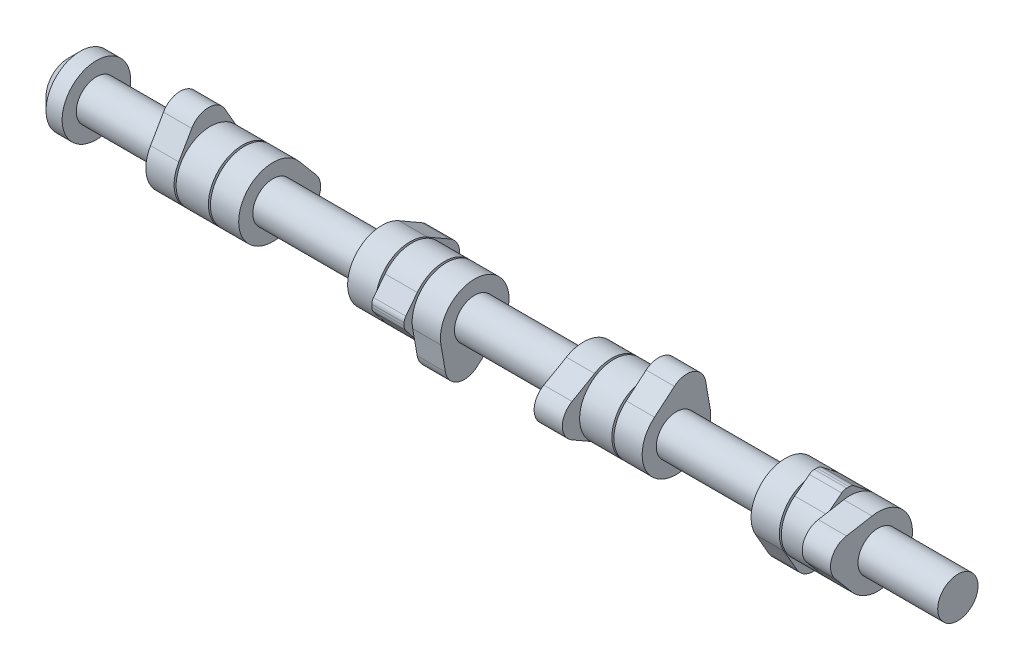
SolidWorks part; units mm, degrees
note: The reader was unsure of these and kept them because the rebuilt part matched: shared geometry of "Sketch1<5>", "Sketch1<6>".
ref_plane "Front Plane" through (0, 0, 0) normal (0, 0, 1) x (1, 0, 0)
ref_plane "Top Plane" through (0, 0, 0) normal (0, 1, 0) x (1, 0, 0)
ref_plane "Right Plane" through (0, 0, 0) normal (1, 0, 0) x (0, 0, -1)
sketch "Sketch1" plane through (0, 0, 0) normal (0, 0, 1) x (1, 0, 0)
  line L0 (0, 0) -> (10, 0)
  line L1 (10, 0) -> (46.5, 0)
  line L2 (46.5, 0) -> (78.5, 0)
  line L3 (78.5, 0) -> (146.5, 0)
  line L4 (146.5, 0) -> (178.5, 0)
  line L5 (178.5, 0) -> (246.5, 0)
  line L6 (246.5, 0) -> (278.5, 0)
  line L7 (278.5, 0) -> (346.5, 0)
  line L8 (346.5, 0) -> (378.5, 0)
  line L9 (378.5, 0) -> (415, 0)
  line L10 (415, 0) -> (425, 0)
  line L11 (39.5, 0) -> (53.5, 0) construction
  line L12 (71.5, 0) -> (85.5, 0) construction
  line L13 (139.5, 0) -> (153.5, 0) construction
  line L14 (185.5, 0) -> (171.5, 0) construction
  line L15 (239.5, 0) -> (253.5, 0)
  line L16 (271.5, 0) -> (285.5, 0)
  line L17 (339.5, 0) -> (353.5, 0)
  line L18 (371.5, 0) -> (385.5, 0)
  line L19 (139.5, 0) -> (139.5, 7)
  line L20 (0, 0) -> (425, 0)
  line L21 (0, 0) -> (0, -10)
  line L22 (0, -10) -> (425, -10)
  line L23 (425, 0) -> (425, -10)
  line L24 (39.5, 0) -> (53.5, 0)
  line L25 (39.5, 0) -> (39.5, 7)
  line L26 (39.5, 7) -> (53.5, 7)
  line L27 (53.5, 0) -> (53.5, 7)
  line L28 (85.5, 0) -> (71.5, 0)
  line L29 (85.5, 0) -> (85.5, 7)
  line L30 (85.5, 7) -> (71.5, 7)
  line L31 (71.5, 0) -> (71.5, 7)
  line L32 (139.5, 0) -> (153.5, 0)
  line L33 (153.5, 0) -> (153.5, 7)
  line L34 (139.5, 7) -> (153.5, 7)
  line L35 (185.5, 0) -> (185.5, 7)
  line L36 (185.5, 0) -> (171.5, 0)
  line L37 (171.5, 0) -> (171.5, 7)
  line L38 (185.5, 7) -> (171.5, 7)
  line L39 (239.5, 0) -> (239.5, 7)
  line L40 (239.5, 0) -> (253.5, 0)
  line L41 (253.5, 0) -> (253.5, 7)
  line L42 (239.5, 7) -> (253.5, 7)
  line L43 (285.5, 0) -> (285.5, 7)
  line L44 (285.5, 0) -> (271.5, 0)
  line L45 (271.5, 0) -> (271.5, 7)
  line L46 (285.5, 7) -> (271.5, 7)
  line L47 (339.5, 0) -> (339.5, 7)
  line L48 (339.5, 0) -> (353.5, 0)
  line L49 (353.5, 0) -> (353.5, 7)
  line L50 (339.5, 7) -> (353.5, 7)
  line L51 (385.5, 0) -> (385.5, 7)
  line L52 (385.5, 0) -> (371.5, 0)
  line L53 (371.5, 0) -> (371.5, 7)
  line L54 (385.5, 7) -> (371.5, 7)
  line L55 (53.5, 0) -> (54.5, 0)
  line L56 (54.5, 0) -> (70.5, 0)
  line L57 (70.5, 0) -> (71.5, 0)
  line L58 (154.5, 0) -> (154.5, 7)
  line L59 (54.5, 0) -> (70.5, 0)
  line L60 (54.5, 0) -> (54.5, 7)
  line L61 (54.5, 7) -> (70.5, 7)
  line L62 (70.5, 0) -> (70.5, 7)
  line L63 (154.5, 0) -> (170.5, 0)
  line L64 (170.5, 0) -> (170.5, 7)
  line L65 (154.5, 7) -> (170.5, 7)
  line L66 (254.5, 0) -> (254.5, 7)
  line L67 (254.5, 0) -> (270.5, 0)
  line L68 (270.5, 0) -> (270.5, 7)
  line L69 (254.5, 7) -> (270.5, 7)
  line L70 (354.5, 0) -> (354.5, 7)
  line L71 (354.5, 0) -> (370.5, 0)
  line L72 (370.5, 0) -> (370.5, 7)
  line L73 (354.5, 7) -> (370.5, 7)
  point P16 (46.5, 0)
  point P19 (78.5, 0)
  point P22 (146.5, 0)
  point P25 (178.5, 0)
  point P28 (246.5, 0)
  point P31 (278.5, 0)
  point P34 (346.5, 0)
  point P37 (378.5, 0)
  dimension "D1" = 10
  dimension "D2" = 36.5
  dimension "D3" = 32
  dimension "D4" = 68
  dimension "D5" = 32
  dimension "D6" = 68
  dimension "D7" = 32
  dimension "D8" = 68
  dimension "D9" = 32
  dimension "D10" = 36.5
  dimension "D11" = 10
  dimension "D12" = 14
  dimension "D13" = 14
  dimension "D14" = 14
  dimension "D15" = 14
  dimension "D16" = 14
  dimension "D17" = 14
  dimension "D18" = 14
  dimension "D19" = 14
  dimension "D20" = 10
  dimension "D21" = 7
  dimension "D23" = 1
  dimension "D24" = 1
  dimension "D25" = 16
  dimension "D22" = 4
  dimension "D26" = 4
revolve "Revolve1" add sketch "Sketch1" angle 360 about L22
revolve "Revolve2" add sketch "Sketch1<5>" angle 360 about L22
sketch "Sketch1<5>" plane through (0, 0, 0) normal (0, 0, 1) x (1, 0, 0) same geometry as "Sketch1"
sketch "Sketch2" plane through (39.5, 0, 0) normal (-1, 0, 0) x (0, 0, 1)
  line L0 (0, 0) -> (0, 7)
  line L1 (0, 7) -> (0, 15)
  line L2 (-6, 15) -> (6, 15)
  line L3 (-6, 15) -> (-17, -10)
  line L4 (-17, -10) -> (0, -10)
  line L5 (0, -10) -> (17, -10)
  line L6 (17, -10) -> (6, 15)
  circle A0 centre (0, -10) radius 17 construction
  point P11 (0, 15)
  circle M4 centre (0, -10) radius 17
  dimension "D1" = 8
  dimension "D2" = 7
  dimension "D3" = 12
extrude "Boss-Extrude2" add sketch "Sketch2" against normal blind 14 contours L6 L2 L1 M4 | L2 L3 L1 M4
fillet "Fillet3" radius 9.5 4 edges at (39.5, 15, 0) (46.5, 15, -6) (46.5, 15, 6) (53.5, 15, 0)
fillet "Fillet5" radius 1000 2 edges at (46.5, 2.5335, 11.4853) (46.5, 2.5335, -11.4853)
sketch "Lobe sketch" plane through (39.5, 0, 0) normal (-1, 0, 0) x (0, 0, 1)
  arc A15 (-14.6833, -1.4325) -> (14.6833, -1.4325) centre (0, -10) ccw
  arc A16 (8.2663, 9.7295) -> (14.6833, -1.4325) centre (878.4044, 502.5375) ccw
  arc A17 (8.2663, 9.7295) -> (-8.2663, 9.7295) centre (0, 5.0479) ccw
  arc A18 (-14.6833, -1.4325) -> (-8.2663, 9.7295) centre (-878.4044, 502.5375) ccw
  arc A19 (-14.6833, -1.4325) -> (14.6833, -1.4325) centre (0, -10) ccw
  arc A20 (8.2663, 9.7295) -> (14.6833, -1.4325) centre (878.4044, 502.5375) ccw
  arc A21 (8.2663, 9.7295) -> (-8.2663, 9.7295) centre (0, 5.0479) ccw
  arc A22 (-14.6833, -1.4325) -> (-8.2663, 9.7295) centre (-878.4044, 502.5375) ccw
  dimension "D1" = 0
sketch "Sketch10" plane through (71.5, 0, 0) normal (-1, 0, 0) x (0, 0, 1)
  circle A1 centre (0, -10) radius 17
  circle A2 centre (0, -10) radius 17
  arc A6 (-14.6833, -1.4325) -> (14.6833, -1.4325) centre (0, -10) ccw
  arc A7 (8.2663, 9.7295) -> (14.6833, -1.4325) centre (878.4044, 502.5375) ccw
  arc A8 (8.2663, 9.7295) -> (-8.2663, 9.7295) centre (0, 5.0479) ccw
  arc A9 (-14.6833, -1.4325) -> (-8.2663, 9.7295) centre (-878.4044, 502.5375) ccw
  arc A10 (-14.6833, -1.4325) -> (14.6833, -1.4325) centre (0, -10) ccw
  arc A11 (8.2663, 9.7295) -> (14.6833, -1.4325) centre (878.4044, 502.5375) ccw
  arc A12 (8.2663, 9.7295) -> (-8.2663, 9.7295) centre (0, 5.0479) ccw
  arc A13 (-14.6833, -1.4325) -> (-8.2663, 9.7295) centre (-878.4044, 502.5375) ccw
  circle M6 centre (0, -10) radius 17
  dimension "D1" = 0
  dimension "D2" = 0
extrude "Boss-Extrude5" add sketch "Sketch10" against normal blind 14 contours A13 A11 A12 M6
sketch "Sketch11" plane through (239.5, 0, 0) normal (-1, 0, 0) x (0, 0, 1)
  circle A3 centre (0, -10) radius 17
  arc A11 (19.7295, -18.2663) -> (19.7295, -1.7337) centre (15.0479, -10) ccw
  arc A12 (19.7295, -18.2663) -> (8.5675, -24.6833) centre (512.5375, -888.4044) ccw
  arc A13 (8.5675, 4.6833) -> (8.5675, -24.6833) centre (0, -10) ccw
  arc A14 (8.5675, 4.6833) -> (19.7295, -1.7337) centre (512.5375, 868.4044) ccw
  circle M6 centre (0, -10) radius 17
extrude "Boss-Extrude6" add sketch "Sketch11" against normal blind 14 contours A14 A12 A11 M6
sketch "Sketch12" plane through (271.5, 0, 0) normal (-1, 0, 0) x (0, 0, 1)
  circle A1 centre (0, -10) radius 17
  circle A2 centre (0, -10) radius 17
  arc A10 (19.7295, -18.2663) -> (19.7295, -1.7337) centre (15.0479, -10) ccw
  arc A11 (19.7295, -18.2663) -> (8.5675, -24.6833) centre (512.5375, -888.4044) ccw
  arc A12 (8.5675, 4.6833) -> (8.5675, -24.6833) centre (0, -10) ccw
  arc A13 (8.5675, 4.6833) -> (19.7295, -1.7337) centre (512.5375, 868.4044) ccw
  dimension "D1" = 0
extrude "Boss-Extrude7" add sketch "Sketch12" against normal blind 14 contours A10 A13 A12 A11
sketch "Sketch13" plane through (339.5, 0, 0) normal (-1, 0, 0) x (0, 0, 1)
  circle A1 centre (0, -10) radius 17
  circle A2 centre (0, -10) radius 17
  arc A10 (-8.2663, -29.7295) -> (8.2663, -29.7295) centre (0, -25.0479) ccw
  arc A11 (-8.2663, -29.7295) -> (-14.6833, -18.5675) centre (-878.4044, -522.5375) ccw
  arc A12 (14.6833, -18.5675) -> (-14.6833, -18.5675) centre (0, -10) ccw
  arc A13 (14.6833, -18.5675) -> (8.2663, -29.7295) centre (878.4044, -522.5375) ccw
  dimension "D1" = 0
sketch "Sketch14" plane through (371.5, 0, 0) normal (-1, 0, 0) x (0, 0, 1)
  circle A1 centre (0, -10) radius 17
  circle A2 centre (0, -10) radius 17
  arc A10 (-8.2663, -29.7295) -> (8.2663, -29.7295) centre (0, -25.0479) ccw
  arc A11 (-8.2663, -29.7295) -> (-14.6833, -18.5675) centre (-878.4044, -522.5375) ccw
  arc A12 (14.6833, -18.5675) -> (-14.6833, -18.5675) centre (0, -10) ccw
  arc A13 (14.6833, -18.5675) -> (8.2663, -29.7295) centre (878.4044, -522.5375) ccw
  dimension "D1" = 0
extrude "Boss-Extrude8" add sketch "Sketch14" against normal blind 14 contours A10 A13 A12 A11
extrude "Boss-Extrude9" add sketch "Sketch13" against normal blind 14 contours A10 A13 A12 A11
sketch "Sketch15" plane through (139.5, 0, 0) normal (-1, 0, 0) x (0, 0, 1)
  arc A8 (-19.7295, -1.7337) -> (-19.7295, -18.2663) centre (-15.0479, -10) ccw
  arc A9 (-19.7295, -1.7337) -> (-8.5675, 4.6833) centre (-512.5375, 868.4044) ccw
  arc A10 (-8.5675, -24.6833) -> (-8.5675, 4.6833) centre (0, -10) ccw
  arc A11 (-8.5675, -24.6833) -> (-19.7295, -18.2663) centre (-512.5375, -888.4044) ccw
sketch "Sketch16" plane through (171.5, 0, 0) normal (-1, 0, 0) x (0, 0, 1)
  arc A8 (-19.7295, -1.7337) -> (-19.7295, -18.2663) centre (-15.0479, -10) ccw
  arc A9 (-19.7295, -1.7337) -> (-8.5675, 4.6833) centre (-512.5375, 868.4044) ccw
  arc A10 (-8.5675, -24.6833) -> (-8.5675, 4.6833) centre (0, -10) ccw
  arc A11 (-8.5675, -24.6833) -> (-19.7295, -18.2663) centre (-512.5375, -888.4044) ccw
extrude "Boss-Extrude10" add sketch "Sketch15" against normal blind 14 contours A8 A11 A10 A9
extrude "Boss-Extrude11" add sketch "Sketch16" against normal blind 14 contours A8 A11 A10 A9
revolve "Revolve3" add sketch "Sketch1<6>" angle 360 about L22
sketch "Sketch1<6>" plane through (0, 0, 0) normal (0, 0, 1) x (1, 0, 0) same geometry as "Sketch1"
sketch "Sketch17" plane through (54.5, 0, 0) normal (-1, 0, 0) x (0, 0, 1)
  line L0 (0, 7) -> (0, 10)
  line L1 (0, 0) -> (0, 7) construction
  line L2 (2, -30) -> (-2, -30)
  line L3 (0, 10) -> (0, -10) construction
  line L4 (17, -10) -> (-17, -10)
  line L5 (17, -10) -> (2, -30)
  line L6 (-2, -30) -> (-17, -10)
  point P8 (0, -30)
  point P15 (0, -10)
  dimension "D1" = 3
  dimension "D2" = 4
extrude "Boss-Extrude12" add sketch "Sketch17" against normal blind 16 contours L2 L6 L4 L5
fillet "Fillet6" radius 1000 2 edges at (62.5, -26.32, -4.76) (62.5, -26.32, 4.76)
fillet "Fillet7" radius 4 2 edges at (62.5, -30, -2) (62.5, -30, 2)
sketch "PD Lobe sketch" plane through (54.5, 0, 0) normal (-1, 0, 0) x (0, 0, 1)
  line L2 (-0.6141, -30) -> (0.6141, -30)
  line L3 (-0.6141, -30) -> (0.6141, -30)
  arc A10 (-3.0867, -29.1442) -> (-10.3846, -23.4596) centre (-621.2411, -815.2009) ccw
  arc A11 (-3.0867, -29.1442) -> (-0.6141, -30) centre (-0.6141, -26) ccw
  arc A12 (0.6141, -30) -> (3.0867, -29.1442) centre (0.6141, -26) ccw
  arc A13 (10.3846, -23.4596) -> (3.0867, -29.1442) centre (621.2411, -815.2009) ccw
  arc A14 (10.3846, -23.4596) -> (-10.3846, -23.4596) centre (0, -10) ccw
  arc A15 (-3.0867, -29.1442) -> (-10.3846, -23.4596) centre (-621.2411, -815.2009) ccw
  arc A16 (-3.0867, -29.1442) -> (-0.6141, -30) centre (-0.6141, -26) ccw
  arc A17 (0.6141, -30) -> (3.0867, -29.1442) centre (0.6141, -26) ccw
  arc A18 (10.3846, -23.4596) -> (3.0867, -29.1442) centre (621.2411, -815.2009) ccw
  arc A19 (10.3846, -23.4596) -> (-10.3846, -23.4596) centre (0, -10) ccw
  dimension "D1" = 0
sketch "Sketch19" plane through (154.5, 0, 0) normal (-1, 0, 0) x (0, 0, 1)
  line L3 (20, -10.6141) -> (20, -9.3859)
  arc A15 (20, -9.3859) -> (19.1442, -6.9133) centre (16, -9.3859) ccw
  arc A16 (13.4596, 0.3846) -> (19.1442, -6.9133) centre (805.2009, 611.2411) ccw
  arc A17 (13.4596, 0.3846) -> (13.4596, -20.3846) centre (0, -10) ccw
  arc A18 (19.1442, -13.0867) -> (13.4596, -20.3846) centre (805.2009, -631.2411) ccw
  arc A19 (19.1442, -13.0867) -> (20, -10.6141) centre (16, -10.6141) ccw
sketch "Sketch20" plane through (254.5, 0, 0) normal (-1, 0, 0) x (0, 0, 1)
  line L2 (-20, -9.3859) -> (-20, -10.6141)
  arc A10 (-20, -10.6141) -> (-19.1442, -13.0867) centre (-16, -10.6141) ccw
  arc A11 (-13.4596, -20.3846) -> (-19.1442, -13.0867) centre (-805.2009, -631.2411) ccw
  arc A12 (-13.4596, -20.3846) -> (-13.4596, 0.3846) centre (0, -10) ccw
  arc A13 (-19.1442, -6.9133) -> (-13.4596, 0.3846) centre (-805.2009, 611.2411) ccw
  arc A14 (-19.1442, -6.9133) -> (-20, -9.3859) centre (-16, -9.3859) ccw
sketch "Sketch21" plane through (354.5, 0, 0) normal (-1, 0, 0) x (0, 0, 1)
  line L2 (0.6141, 10) -> (-0.6141, 10)
  arc A10 (-0.6141, 10) -> (-3.0867, 9.1442) centre (-0.6141, 6) ccw
  arc A11 (-10.3846, 3.4596) -> (-3.0867, 9.1442) centre (-621.2411, 795.2009) ccw
  arc A12 (-10.3846, 3.4596) -> (10.3846, 3.4596) centre (0, -10) ccw
  arc A13 (3.0867, 9.1442) -> (10.3846, 3.4596) centre (621.2411, 795.2009) ccw
  arc A14 (3.0867, 9.1442) -> (0.6141, 10) centre (0.6141, 6) ccw
extrude "Boss-Extrude13" add sketch "Sketch21" against normal blind 16
extrude "Boss-Extrude14" add sketch "Sketch20" against normal blind 16
extrude "Boss-Extrude15" add sketch "Sketch19" against normal blind 16
sketch "Sketch22" plane through (0, 0, 0) normal (-1, 0, 0) x (0, 0, 1)
  circle A0 centre (0, -10) radius 17
extrude "Front" add sketch "Sketch22" along normal blind 16 contours A0
chamfer "Chamfer1" distance 6 angle 45 1 edges at (-16, -10, 17)
sketch "Sketch23" plane through (-16, 0, 0) normal (-1, 0, 0) x (0, 0, 1)
  circle A0 centre (0, -10) radius 6
  dimension "D1" = 12
extrude "Cut-Extrude1" cut sketch "Sketch23" against normal blind 40 contours A0
sketch "Sketch24" plane through (0, 0, 0) normal (1, 0, 0) x (0, 0, -1)
  circle A0 centre (0, -10) radius 10
  circle A1 centre (0, -10) radius 17
extrude "Cut-Extrude2" cut sketch "Sketch24" against normal blind 2
sketch "Sketch25" plane through (-16, 0, 0) normal (-1, 0, 0) x (0, 0, 1)
  line L0 (0, -10) -> (-24.5479, -10)
  arc A0 (-19.7295, -1.7337) -> (-19.7295, -18.2663) centre (-15.0479, -10) ccw construction
  dimension "D1" = 24.5479
sketch "Sketch26" plane through (71.5, 0, 0) normal (-1, 0, 0) x (0, 0, 1)
  arc A8 (-3.0288, -26.728) -> (-13.0728, 0.8675) centre (0, -10) ccw
  arc A9 (-21.3669, -8.9801) -> (-13.0728, 0.8675) centre (-782.0597, 640.132) ccw
  arc A10 (-21.3669, -8.9801) -> (-15.7125, -24.5157) centre (-14.1404, -15.1467) ccw
  arc A11 (-3.0288, -26.728) -> (-15.7125, -24.5157) centre (-181.1957, -1010.7283) ccw
sketch "Sketch28" plane through (71.5, 0, 0) normal (-1, 0, 0) x (0, 0, 1)
  arc A8 (-14.6833, -1.4325) -> (14.6833, -1.4325) centre (0, -10) ccw
  arc A9 (8.2663, 9.7295) -> (14.6833, -1.4325) centre (878.4044, 502.5375) ccw
  arc A10 (8.2663, 9.7295) -> (-8.2663, 9.7295) centre (0, 5.0479) ccw
  arc A11 (-14.6833, -1.4325) -> (-8.2663, 9.7295) centre (-878.4044, 502.5375) ccw
  arc A12 (-14.6833, -1.4325) -> (14.6833, -1.4325) centre (0, -10) ccw
  arc A13 (8.2663, 9.7295) -> (14.6833, -1.4325) centre (878.4044, 502.5375) ccw
  arc A14 (8.2663, 9.7295) -> (-8.2663, 9.7295) centre (0, 5.0479) ccw
  arc A15 (-14.6833, -1.4325) -> (-8.2663, 9.7295) centre (-878.4044, 502.5375) ccw
  dimension "D1" = 0
extrude "Cut-Extrude4" cut sketch "Sketch28" against normal blind 14
extrude "Boss-Extrude16" add sketch "Sketch26" against normal blind 14
sketch "Sketch29" plane through (171.5, 0, 0) normal (-1, 0, 0) x (0, 0, 1)
  arc A4 (-8.5675, -24.6833) -> (-8.5675, 4.6833) centre (0, -10) ccw
  arc A5 (-19.7295, -1.7337) -> (-8.5675, 4.6833) centre (-512.5375, 868.4044) ccw
  arc A6 (-19.7295, -1.7337) -> (-19.7295, -18.2663) centre (-15.0479, -10) ccw
  arc A7 (-8.5675, -24.6833) -> (-19.7295, -18.2663) centre (-512.5375, -888.4044) ccw
  arc A8 (-8.5675, -24.6833) -> (-8.5675, 4.6833) centre (0, -10) ccw
  arc A9 (-19.7295, -1.7337) -> (-8.5675, 4.6833) centre (-512.5375, 868.4044) ccw
  arc A10 (-19.7295, -1.7337) -> (-19.7295, -18.2663) centre (-15.0479, -10) ccw
  arc A11 (-8.5675, -24.6833) -> (-19.7295, -18.2663) centre (-512.5375, -888.4044) ccw
  dimension "D1" = 0
sketch "Sketch30" plane through (171.5, 0, 0) normal (-1, 0, 0) x (0, 0, 1)
  arc A12 (16.728, -13.0288) -> (-10.8675, -23.0728) centre (0, -10) ccw
  arc A13 (-1.0199, -31.3669) -> (-10.8675, -23.0728) centre (-650.132, -792.0597) ccw
  arc A14 (-1.0199, -31.3669) -> (14.5157, -25.7125) centre (5.1467, -24.1404) ccw
  arc A15 (16.728, -13.0288) -> (14.5157, -25.7125) centre (1000.7283, -191.1957) ccw
extrude "Cut-Extrude5" cut sketch "Sketch29" against normal blind 14
extrude "Boss-Extrude17" add sketch "Sketch30" against normal blind 14
sketch "Sketch31" plane through (271.5, 0, 0) normal (-1, 0, 0) x (0, 0, 1)
  arc A4 (8.5675, 4.6833) -> (8.5675, -24.6833) centre (0, -10) ccw
  arc A5 (19.7295, -18.2663) -> (8.5675, -24.6833) centre (512.5375, -888.4044) ccw
  arc A6 (19.7295, -18.2663) -> (19.7295, -1.7337) centre (15.0479, -10) ccw
  arc A7 (8.5675, 4.6833) -> (19.7295, -1.7337) centre (512.5375, 868.4044) ccw
  arc A8 (8.5675, 4.6833) -> (8.5675, -24.6833) centre (0, -10) ccw
  arc A9 (19.7295, -18.2663) -> (8.5675, -24.6833) centre (512.5375, -888.4044) ccw
  arc A10 (19.7295, -18.2663) -> (19.7295, -1.7337) centre (15.0479, -10) ccw
  arc A11 (8.5675, 4.6833) -> (19.7295, -1.7337) centre (512.5375, 868.4044) ccw
  dimension "D1" = 0
sketch "Sketch32" plane through (271.5, 0, 0) normal (-1, 0, 0) x (0, 0, 1)
  arc A8 (-16.728, -6.9712) -> (10.8675, 3.0728) centre (0, -10) ccw
  arc A9 (1.0199, 11.3669) -> (10.8675, 3.0728) centre (650.132, 772.0597) ccw
  arc A10 (1.0199, 11.3669) -> (-14.5157, 5.7125) centre (-5.1467, 4.1404) ccw
  arc A11 (-16.728, -6.9712) -> (-14.5157, 5.7125) centre (-1000.7283, 171.1957) ccw
extrude "Cut-Extrude6" cut sketch "Sketch31" against normal blind 14
extrude "Boss-Extrude18" add sketch "Sketch32" against normal blind 14
sketch "Sketch33" plane through (371.5, 0, 0) normal (-1, 0, 0) x (0, 0, 1)
  arc A4 (14.6833, -18.5675) -> (-14.6833, -18.5675) centre (0, -10) ccw
  arc A5 (-8.2663, -29.7295) -> (-14.6833, -18.5675) centre (-878.4044, -522.5375) ccw
  arc A6 (-8.2663, -29.7295) -> (8.2663, -29.7295) centre (0, -25.0479) ccw
  arc A7 (14.6833, -18.5675) -> (8.2663, -29.7295) centre (878.4044, -522.5375) ccw
  arc A8 (14.6833, -18.5675) -> (-14.6833, -18.5675) centre (0, -10) ccw
  arc A9 (-8.2663, -29.7295) -> (-14.6833, -18.5675) centre (-878.4044, -522.5375) ccw
  arc A10 (-8.2663, -29.7295) -> (8.2663, -29.7295) centre (0, -25.0479) ccw
  arc A11 (14.6833, -18.5675) -> (8.2663, -29.7295) centre (878.4044, -522.5375) ccw
  dimension "D1" = 0
sketch "Sketch34" plane through (371.5, 0, 0) normal (-1, 0, 0) x (0, 0, 1)
  arc A8 (3.0288, 6.728) -> (13.0728, -20.8675) centre (0, -10) ccw
  arc A9 (21.3669, -11.0199) -> (13.0728, -20.8675) centre (782.0597, -660.132) ccw
  arc A10 (21.3669, -11.0199) -> (15.7125, 4.5157) centre (14.1404, -4.8533) ccw
  arc A11 (3.0288, 6.728) -> (15.7125, 4.5157) centre (181.1957, 990.7283) ccw
extrude "Cut-Extrude7" cut sketch "Sketch33" against normal blind 14
extrude "Boss-Extrude19" add sketch "Sketch34" against normal blind 14
